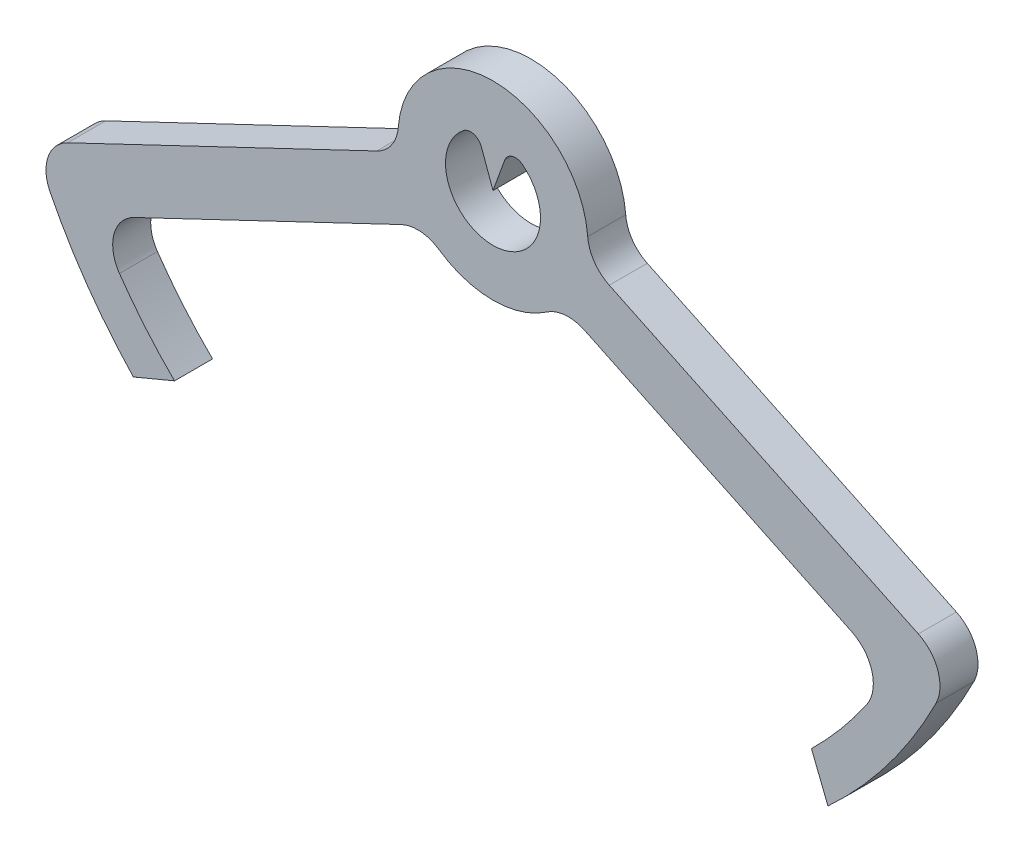
SolidWorks part; units mm, degrees
ref_plane "Front Plane" through (0, 0, 0) normal (0, 0, 1) x (1, 0, 0)
ref_plane "Top Plane" through (0, 0, 0) normal (0, 1, 0) x (1, 0, 0)
ref_plane "Right Plane" through (0, 0, 0) normal (1, 0, 0) x (0, 0, -1)
sketch "Sketch1" plane through (0, 0, 0) normal (0, 0, 1) x (1, 0, 0)
  line L0 (17.8779, -42.7612) -> (-94.6262, -89.7976) construction
  line L1 (43.0668, 17.1286) -> (88.1318, -96.1796) construction
  line L2 (-83.792, -85.268) -> (-94.6262, -89.7976)
  line L3 (83.792, -85.268) -> (88.1318, -96.1796)
  line L4 (-117.7439, -56.1614) -> (0, 0) construction
  line L5 (0, 0) -> (117.7439, -56.1614) construction
  line L6 (-104.4607, -58.1351) -> (-18.2964, -17.0365)
  line L7 (-120.778, -49.2992) -> (-24.7541, -3.4977)
  line L8 (24.7541, -3.4977) -> (120.778, -49.2992)
  line L9 (18.2964, -17.0365) -> (104.4607, -58.1351)
  line L10 (0, 0) -> (0, 119.548) construction
  line L11 (-83.792, -85.268) -> (0, 0) construction
  line L12 (-4.2753, 11.7462) -> (0, 0)
  line L13 (0, 0) -> (4.2753, 11.7462)
  circle A0 centre (0, 0) radius 46.348 construction
  circle A1 centre (0, 0) radius 130.452 construction
  circle A2 centre (0, 0) radius 119.548 construction
  arc A3 (-83.792, -85.268) -> (-104.4607, -58.1351) centre (0, 0) cw
  arc A4 (-94.6262, -89.7976) -> (-120.778, -49.2992) centre (0, 0) cw
  arc A5 (83.792, -85.268) -> (104.4607, -58.1351) centre (0, 0) ccw
  arc A6 (88.1318, -96.1796) -> (120.778, -49.2992) centre (0, 0) ccw
  circle A7 centre (0, 0) radius 25
  circle A8 centre (0, 0) radius 12.5
  point P9 (-83.792, -85.268)
  point P10 (83.792, -85.268)
  dimension "impulse base circle" = 92.696
  dimension "external arc" = 260.904
  dimension "internal arc" = 239.096
  dimension "D6" = 25
  dimension "D7" = 50
  dimension "pallet opening" = 167.584
  dimension "arm thickness" = 15
  dimension "D1" = 15
  dimension "D2" = 7.5
  dimension "D3" = 7.5
  dimension "D4" = 115.5
  dimension "D5" = 115.5
  dimension "clearance angle" = 20
  dimension "D8" = 20
  dimension "D9" = 20
extrude "Boss-Extrude1" add sketch "Sketch1" along normal blind 10 contours A7 L7 A4 L2 A3 L6 | A7 A8 | A7 L9 A5 L3 A6 L8 | L13 A8 L12 region at (-75.6022, -41.1208, 0) region at (-21.9264, -10.4584, 0) region at (75.9316, -42.3447, 0) region at (0, 8.1651, 0)
fillet "Fillet1" radius 10 4 edges at (-18.2964, -17.0365, 5) (18.2964, -17.0365, 5) (24.7541, -3.4977, 5) (-24.7541, -3.4977, 5)
fillet "Fillet2" radius 10 4 edges at (120.778, -49.2992, 5) (104.4607, -58.1351, 5) (-104.4607, -58.1351, 5) (-120.778, -49.2992, 5)
fillet "Fillet3" radius 3 2 edges at (4.2753, 11.7462, 5) (-4.2753, 11.7462, 5)
ref_axis "Axis1" through (0, 0, 0) along (0, 0, 1)
equation "\"D1@Sketch1\"=\"arm thickness@Sketch1\""
equation "\"D2@Sketch1\"=\"arm thickness@Sketch1\"*0.5"
equation "\"D3@Sketch1\"=\"arm thickness@Sketch1\"*0.5"
equation "\"D5@Sketch1\"=\"D4@Sketch1\""
equation "\"D9@Sketch1\"=\"D8@Sketch1\""
